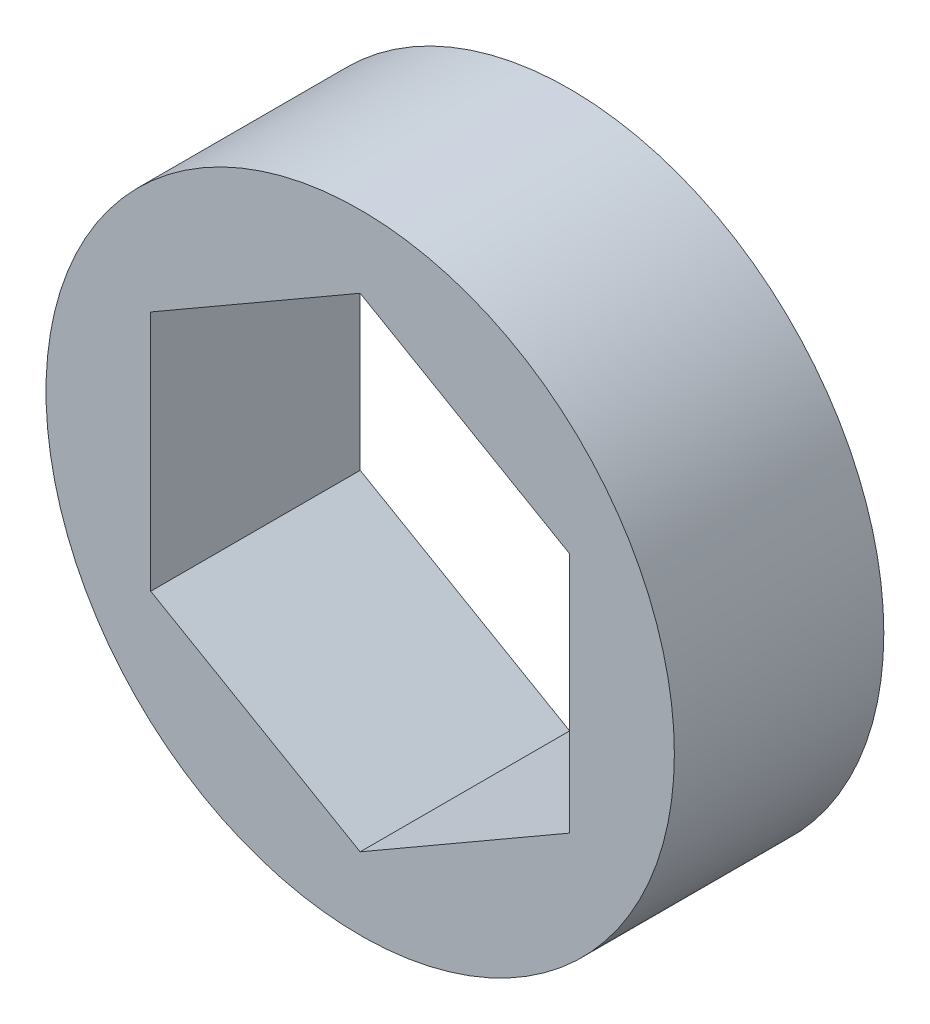
SolidWorks part; units mm, degrees
ref_plane "Front Plane" through (0, 0, 0) normal (0, 0, 1) x (1, 0, 0)
ref_plane "Top Plane" through (0, 0, 0) normal (0, 1, 0) x (1, 0, 0)
ref_plane "Right Plane" through (0, 0, 0) normal (1, 0, 0) x (0, 0, -1)
sketch "Sketch2" plane through (0, 0, 0) normal (0, 0, 1) x (1, 0, 0)
  line L1 (0, 7.3323) -> (-6.35, 3.6662)
  line L2 (-6.35, 3.6662) -> (-6.35, -3.6662)
  line L3 (-6.35, -3.6662) -> (0, -7.3323)
  line L4 (0, -7.3323) -> (6.35, -3.6662)
  line L5 (6.35, -3.6662) -> (6.35, 3.6662)
  line L6 (6.35, 3.6662) -> (0, 7.3323)
  circle A0 centre (0, 0) radius 6.35 construction
  circle A1 centre (0, 0) radius 9.525
  point P10 (0, 0)
  dimension "D1" = 19.05
  dimension ".5" = 12.7
extrude "Boss-Extrude1" add sketch "Sketch2" along normal blind 6.35
